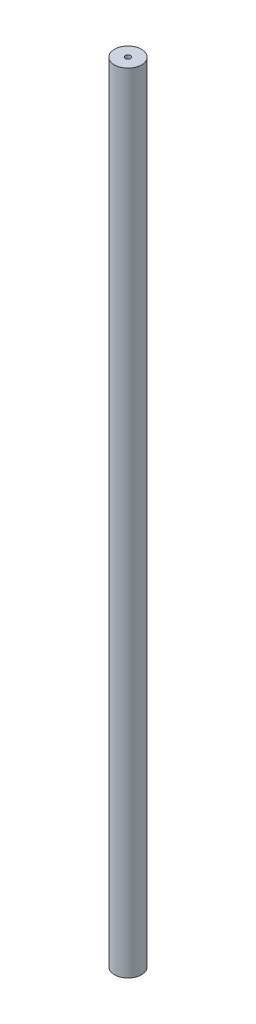
SolidWorks part; units mm, degrees
ref_plane "Front Plane" through (0, 0, 0) normal (0, 0, 1) x (1, 0, 0)
ref_plane "Top Plane" through (0, 0, 0) normal (0, 1, 0) x (1, 0, 0)
ref_plane "Right Plane" through (0, 0, 0) normal (1, 0, 0) x (0, 0, -1)
sketch "Sketch1" plane through (0, 0, 0) normal (0, 1, 0) x (1, 0, 0)
  circle A0 centre (0, 0) radius 12.7
  circle A1 centre (0, 0) radius 2.5
  dimension "D1" = 25.4
  dimension "D2" = 5
extrude "Boss-Extrude1" add sketch "Sketch1" along normal blind 738
